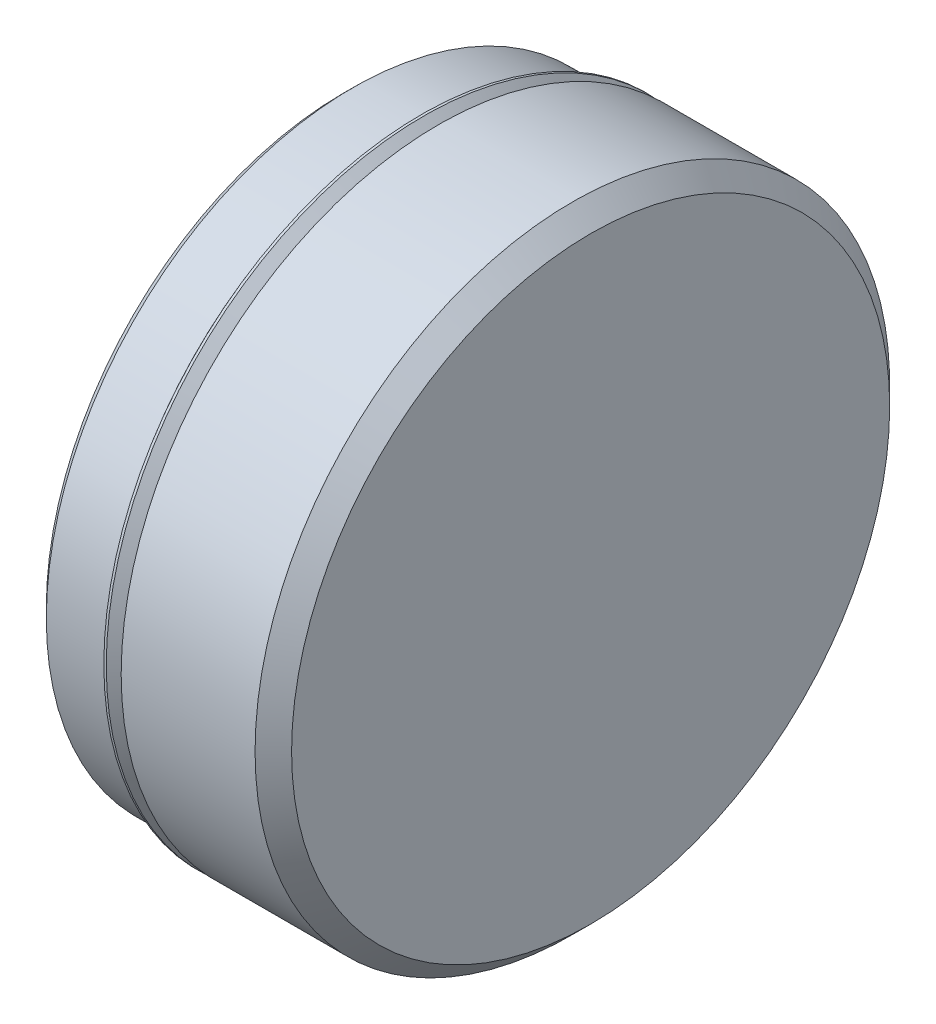
SolidWorks part; units mm, degrees
material "Cast Alloy Steel"
ref_plane "Front Plane" through (0, 0, 0) normal (0, 0, 1) x (1, 0, 0)
ref_plane "Top Plane" through (0, 0, 0) normal (0, 1, 0) x (1, 0, 0)
ref_plane "Right Plane" through (0, 0, 0) normal (1, 0, 0) x (0, 0, -1)
sketch "Sketch1" plane through (0, 0, 0) normal (0, 0, 1) x (1, 0, 0)
  line L0 (0, 0) -> (0, 24.8095)
  line L1 (0, 24.8095) -> (0.762, 25.5714)
  line L2 (0.762, 25.5714) -> (5.8166, 25.5714)
  line L3 (5.8166, 25.5714) -> (6.8707, 24.5174)
  line L4 (6.8707, 24.5174) -> (7.9248, 24.5174)
  line L5 (7.9248, 24.5174) -> (7.9248, 26.4858)
  line L6 (7.9248, 26.4858) -> (19.1008, 26.4858)
  line L7 (19.1008, 26.4858) -> (20.6248, 24.9618)
  line L8 (20.6248, 24.9618) -> (20.6248, 0)
  line L9 (20.6248, 0) -> (0, 0)
  line L10 (20.6248, 0) -> (0, 0) construction
revolve "Revolve1" add sketch "Sketch1" angle 360 about L10 reverse direction yes
ref_plane "Plane1" through (20.6248, 0, 0) normal (1, 0, 0) x (0, 0, -1)
ref_plane "Plane2" through (30.2006, 0, 0) normal (1, 0, 0) x (0, 0, -1)
ref_plane "Plane3" through (0, 0, 0) normal (0, 0.9998, 0.0175) x (1, 0, 0)
ref_plane "Plane4" through (18.2626, 0, 0) normal (1, 0, 0) x (0, 0, -1)
ref_plane "Plane5" through (6.8707, 0, 0) normal (1, 0, 0) x (0, 0, -1)
sketch "Sketch2" plane through (0, 0, 0) normal (0, 0, 1) x (1, 0, 0)
  line L0 (6.4771, 26.4017) -> (7.7898, 25.089)
  line L1 (7.7898, 24.9094) -> (7.3978, 24.5174)
  line L2 (7.3978, 24.5174) -> (6.8707, 24.5174)
  line L3 (6.8707, 24.5174) -> (6.8707, 24.2634)
  line L4 (6.8707, 24.2634) -> (7.9248, 24.2634)
  line L5 (7.9248, 24.2634) -> (7.9248, 25.2413)
  line L6 (7.9248, 25.2413) -> (6.6803, 26.4858)
  line L7 (6.6803, 26.4858) -> (6.4771, 26.4858)
  line L8 (6.4771, 26.4858) -> (6.4771, 26.4017)
  line L9 (7.9248, 0) -> (6.8707, 0) construction
  arc A0 (7.7898, 25.089) -> (7.7898, 24.9094) centre (7.7, 24.9992) cw
revolve "Revolve2" add sketch "Sketch2" angle 360 about L9 reverse direction yes
ref_plane "Plane6" through (20.7518, 0, 0) normal (1, 0, 0) x (0, 0, -1)
sketch "Sketch3" plane through (0, 0, 0) normal (0, 0, 1) x (1, 0, 0)
  line L0 (0, 0) -> (0, 20.5994)
  line L1 (0, 20.5994) -> (0.762, 19.8374)
  line L2 (0.762, 19.8374) -> (3.175, 19.8374)
  line L3 (3.175, 19.8374) -> (3.175, 16.5926)
  line L4 (3.175, 16.5926) -> (3.937, 15.8306)
  line L5 (3.937, 15.8306) -> (12.7, 15.8306)
  line L6 (12.7, 15.8306) -> (12.7, 0)
  line L7 (12.7, 0) -> (0, 0)
  line L8 (12.7, 0) -> (0, 0) construction
revolve "Cut-Revolve1" cut sketch "Sketch3" angle 360 about L8 reverse direction yes
ref_plane "Plane7" through (0, 0, 0) normal (1, 0, 0) x (0, 0, -1)
ref_plane "Plane8" through (12.7, 0, 0) normal (1, 0, 0) x (0, 0, -1)
ref_plane "Plane9" through (20.6248, 0, 0) normal (1, 0, 0) x (0, 0, -1)
ref_plane "Plane10" through (0, 0, 0) normal (0, 1, 0) x (1, 0, 0)
ref_plane "Plane11" through (0, 0.1016, 0) normal (0, 1, 0) x (1, 0, 0)
ref_plane "Plane12" through (30.2006, 0, 0) normal (1, 0, 0) x (0, 0, -1)
ref_plane "lovra XY" through (20.6248, 0, 0) normal (1, 0, 0) x (0, 0, -1)
ref_plane "lovra XZ" through (0, 0, 0) normal (0, 0, -1) x (-1, 0, 0)
ref_plane "lovra YZ" through (0, 0, 0) normal (0, 1, 0) x (1, 0, 0)
ref_axis "lovra X" through (20.6248, -50, 0) along (0, 1, 0)
ref_axis "lovra Y" through (20.6248, 0, -80.9) along (0, 0, 1)
ref_axis "lovra Z" through (80.9, 0, 0) along (-1, 0, 0)
sketch3d "lovra"
  point P0 (20.6248, 0, 0)
ref_plane "lovra1 XY" through (12.7, 0, 0) normal (1, 0, 0) x (0, 0, -1)
ref_plane "lovra1 XZ" through (0, 0, 0) normal (0, -1, 0) x (-1, 0, 0)
ref_plane "lovra1 YZ" through (0, 0, 0) normal (0, 0, -1) x (-1, 0, 0)
ref_axis "lovra1 X" through (12.7, 0, 80.9) along (0, 0, -1)
ref_axis "lovra1 Y" through (12.7, -50, 0) along (0, 1, 0)
ref_axis "lovra1 Z" through (80.9, 0, 0) along (-1, 0, 0)
sketch3d "lovra1"
  point P0 (12.7, 0, 0)
ref_plane "lovra2 XY" through (12.7, 0, 0) normal (1, 0, 0) x (0, 0, -1)
ref_plane "lovra2 XZ" through (0, 15.748, 0) normal (0, -1, 0) x (-1, 0, 0)
ref_plane "lovra2 YZ" through (0, 0, 0) normal (0, 0, -1) x (-1, 0, 0)
ref_axis "lovra2 X" through (12.7, 15.748, 80.9) along (0, 0, -1)
ref_axis "lovra2 Y" through (12.7, -50, 0) along (0, 1, 0)
ref_axis "lovra2 Z" through (80.9, 15.748, 0) along (-1, 0, 0)
sketch3d "lovra2"
  point P0 (12.7, 15.748, 0)
ref_plane "lovra21 XY" through (0, 0, 0) normal (1, 0, 0) x (0, 0, -1)
ref_plane "lovra21 XZ" through (0, 0, 0) normal (0, -1, 0) x (-1, 0, 0)
ref_plane "lovra21 YZ" through (0, 0, 5.2705) normal (0, 0, -1) x (-1, 0, 0)
ref_axis "lovra21 X" through (0, 0, 80.9) along (0, 0, -1)
ref_axis "lovra21 Y" through (0, -50, 5.2705) along (0, 1, 0)
ref_axis "lovra21 Z" through (80.9, 0, 5.2705) along (-1, 0, 0)
sketch3d "lovra21"
  point P0 (0, 0, 5.2705)
ref_plane "lovra22 XY" through (0, 0, 0) normal (1, 0, 0) x (0, 0, -1)
ref_plane "lovra22 XZ" through (0, 0, 0) normal (0, -1, 0) x (-1, 0, 0)
ref_plane "lovra22 YZ" through (0, 0, -5.2705) normal (0, 0, -1) x (-1, 0, 0)
ref_axis "lovra22 X" through (0, 0, 80.9) along (0, 0, -1)
ref_axis "lovra22 Y" through (0, -50, -5.2705) along (0, 1, 0)
ref_axis "lovra22 Z" through (80.9, 0, -5.2705) along (-1, 0, 0)
sketch3d "lovra22"
  point P0 (0, 0, -5.2705)
ref_plane "lovra3 XY" through (12.7, 0, 0) normal (1, 0, 0) x (0, 0, -1)
ref_plane "lovra3 XZ" through (0, -15.748, 0) normal (0, -1, 0) x (-1, 0, 0)
ref_plane "lovra3 YZ" through (0, 0, 0) normal (0, 0, -1) x (-1, 0, 0)
ref_axis "lovra3 X" through (12.7, -15.748, 80.9) along (0, 0, -1)
ref_axis "lovra3 Y" through (12.7, -50, 0) along (0, 1, 0)
ref_axis "lovra3 Z" through (80.9, -15.748, 0) along (-1, 0, 0)
sketch3d "lovra3"
  point P0 (12.7, -15.748, 0)
ref_plane "olen XY" through (20.6248, 0, 0) normal (1, 0, 0) x (0, 0, -1)
ref_plane "olen XZ" through (0, 0, 0) normal (0, -1, 0) x (-1, 0, 0)
ref_plane "olen YZ" through (0, 0, 0) normal (0, 0, -1) x (-1, 0, 0)
ref_axis "olen X" through (20.6248, 0, 80.9) along (0, 0, -1)
ref_axis "olen Y" through (20.6248, -50, 0) along (0, 1, 0)
ref_axis "olen Z" through (80.9, 0, 0) along (-1, 0, 0)
sketch3d "olen"
  point P0 (20.6248, 0, 0)
ref_plane "to_mounting_bracket XY" through (30.2006, 0, 0) normal (1, 0, 0) x (0, 0, -1)
ref_plane "to_mounting_bracket XZ" through (0, 0, 0) normal (0, -1, 0) x (-1, 0, 0)
ref_plane "to_mounting_bracket YZ" through (0, 0, 0) normal (0, 0, -1) x (-1, 0, 0)
ref_axis "to_mounting_bracket X" through (30.2006, 0, 80.9) along (0, 0, -1)
ref_axis "to_mounting_bracket Y" through (30.2006, -50, 0) along (0, 1, 0)
ref_axis "to_mounting_bracket Z" through (80.9, 0, 0) along (-1, 0, 0)
sketch3d "to_mounting_bracket"
  point P0 (30.2006, 0, 0)
ref_plane "to_nut XY" through (0, 0, 0) normal (1, 0, 0) x (0, 0, -1)
ref_plane "to_nut XZ" through (0, 0, 0) normal (0, -1, 0) x (-1, 0, 0)
ref_plane "to_nut YZ" through (0, 0, 0) normal (0, 0, -1) x (-1, 0, 0)
ref_axis "to_nut X" through (0, 0, 80.9) along (0, 0, -1)
ref_axis "to_nut Y" through (0, -50, 0) along (0, 1, 0)
ref_axis "to_nut Z" through (80.9, 0, 0) along (-1, 0, 0)
sketch3d "to_nut"
  point P0 (0, 0, 0)
ref_plane "to_pin XY" through (0, 0, 0) normal (0, 0, 1) x (1, 0, 0)
ref_plane "to_pin XZ" through (0, 0, 0) normal (0, -1, 0) x (-1, 0, 0)
ref_plane "to_pin YZ" through (44.45, 0, 0) normal (1, 0, 0) x (0, 0, -1)
ref_axis "to_pin X" through (-80.9, 0, 0) along (1, 0, 0)
ref_axis "to_pin Y" through (44.45, -50, 0) along (0, 1, 0)
ref_axis "to_pin Z" through (44.45, 0, 80.9) along (0, 0, -1)
sketch3d "to_pin"
  point P0 (44.45, 0, 0)
ref_plane "to_screw XY" through (0, 0.1016, 0) normal (0, 1, 0) x (1, 0, 0)
ref_plane "to_screw XZ" through (0, 0, -14.1986) normal (0, 0, 1) x (1, 0, 0)
ref_plane "to_screw YZ" through (18.2626, 0, 0) normal (1, 0, 0) x (0, 0, -1)
ref_axis "to_screw X" through (-80.9, 0.1016, -14.1986) along (1, 0, 0)
ref_axis "to_screw Y" through (18.2626, 0.1016, 50) along (0, 0, -1)
ref_axis "to_screw Z" through (18.2626, 50, -14.1986) along (0, -1, 0)
sketch3d "to_screw"
  point P0 (18.2626, 0.1016, -14.1986)
ref_plane "to_tube XY" through (6.8707, 0, 0) normal (1, 0, 0) x (0, 0, -1)
ref_plane "to_tube XZ" through (0, 0, 0) normal (0, -1, 0) x (-1, 0, 0)
ref_plane "to_tube YZ" through (0, 0, 0) normal (0, 0, -1) x (-1, 0, 0)
ref_axis "to_tube X" through (6.8707, 0, 80.9) along (0, 0, -1)
ref_axis "to_tube Y" through (6.8707, -50, 0) along (0, 1, 0)
ref_axis "to_tube Z" through (80.9, 0, 0) along (-1, 0, 0)
sketch3d "to_tube"
  point P0 (6.8707, 0, 0)
